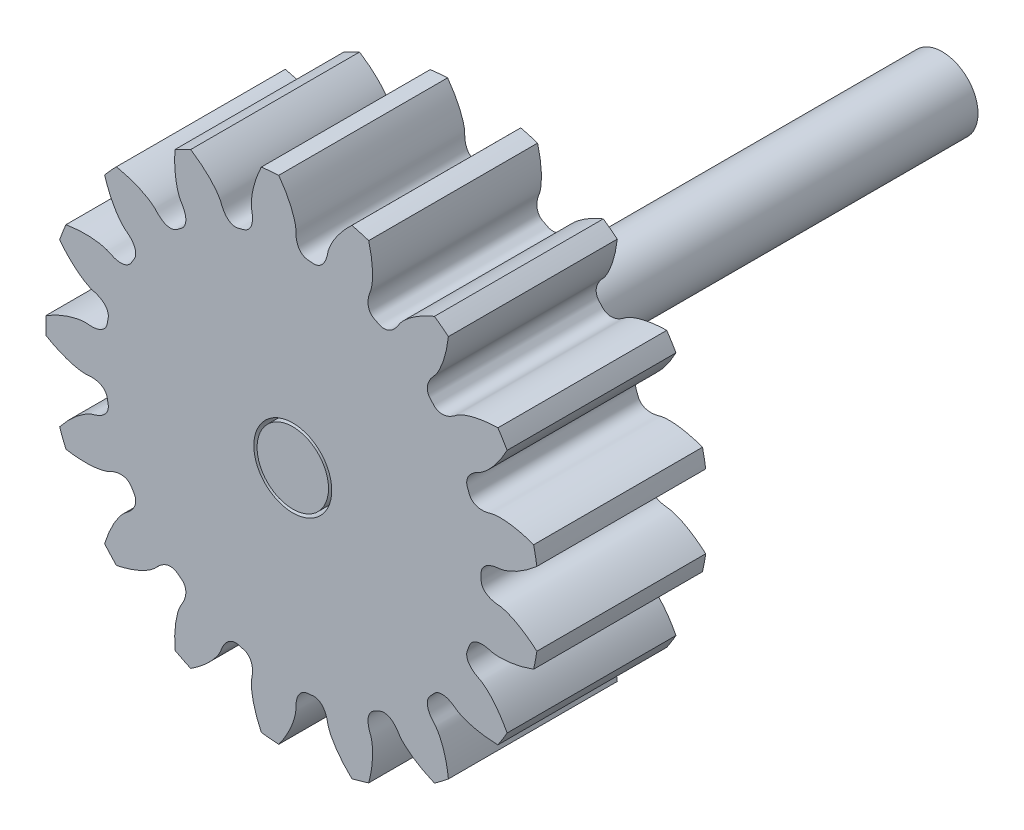
SolidWorks part; units mm, degrees
ref_plane "Front Plane" through (0, 0, 0) normal (0, 0, 1) x (1, 0, 0)
ref_plane "Top Plane" through (0, 0, 0) normal (0, 1, 0) x (1, 0, 0)
ref_plane "Right Plane" through (0, 0, 0) normal (1, 0, 0) x (0, 0, -1)
ref_axis "Axis1" through (0, 0, 55) along (0, 0, -1)
sketch "旋转草图大直齿轮" plane through (0, 0, 0) normal (1, 0, 0) x (0, 0, -1)
  line L0 (0, 0) -> (1, 0) construction
  line L1 (-10, 0) -> (-10, 19)
  line L2 (-10, 19) -> (3, 19)
  line L3 (3, 19) -> (3, 0)
  line L4 (3, 0) -> (-10, 0)
  dimension "Side1" = 10
  dimension "OutsideRadius" = 19
  dimension "Side2" = 3
revolve "大直齿轮" add sketch "旋转草图大直齿轮" angle 360 about L0
sketch "齿草图大直齿轮" plane through (0, 0, 0) normal (0, 0, 1) x (1, 0, 0)
  arc A0 (18.8777, 2.9059) -> (18.8777, -2.9059) centre (0, 0) cw
  spline S0 degree 3 poles (18.8777, -2.9059) (18.7162, -2.7605) (18.4737, -2.5555) (18.1462, -2.3058) (17.9156, -2.1416) (17.694, -1.9946) (17.4824, -1.8638) (17.2814, -1.7487) (17.092, -1.6481) (16.9148, -1.5614) (16.7504, -1.4876) (16.5997, -1.4257) (16.463, -1.3747) (16.3411, -1.3337) (16.2343, -1.3016) (16.143, -1.2774) (16.0678, -1.2601) (16.0089, -1.2485) (15.9082, -1.2318) (15.8073, -1.2291) (15.7037, -1.216) (15.6495, -1.2083) (15.5963, -1.1996) (15.544, -1.19) (15.4927, -1.1794) (15.4423, -1.1677) (15.3928, -1.1551) (15.3442, -1.1414) (15.2965, -1.1266) (15.2496, -1.1108) (15.2035, -1.0937) (15.1582, -1.0755) (15.1136, -1.056) (15.0698, -1.0351) (15.0267, -1.0127) (14.9843, -0.9888) (14.9426, -0.9632) (14.9016, -0.9357) (14.8613, -0.9062) (14.8218, -0.8744) (14.7832, -0.8402) (14.7455, -0.8034) (14.709, -0.7636) (14.674, -0.7206) (14.6407, -0.6743) (14.6095, -0.6245) (14.581, -0.5711) (14.5558, -0.5142) (14.5343, -0.4538) (14.5174, -0.3904) (14.5054, -0.3246) (14.4997, -0.2626) (14.4972, -0.1542) (14.5022, 0) (14.4972, 0.1542) (14.4997, 0.2626) (14.5054, 0.3246) (14.5174, 0.3904) (14.5343, 0.4538) (14.5558, 0.5142) (14.581, 0.5711) (14.6095, 0.6245) (14.6407, 0.6743) (14.674, 0.7206) (14.709, 0.7636) (14.7455, 0.8034) (14.7832, 0.8402) (14.8218, 0.8744) (14.8613, 0.9062) (14.9016, 0.9357) (14.9426, 0.9632) (14.9843, 0.9888) (15.0267, 1.0127) (15.0698, 1.0351) (15.1136, 1.056) (15.1582, 1.0755) (15.2035, 1.0937) (15.2496, 1.1108) (15.2965, 1.1266) (15.3442, 1.1414) (15.3928, 1.1551) (15.4423, 1.1677) (15.4927, 1.1794) (15.544, 1.19) (15.5963, 1.1996) (15.6495, 1.2083) (15.7037, 1.216) (15.8073, 1.2291) (15.9082, 1.2318) (16.0089, 1.2485) (16.0678, 1.2601) (16.143, 1.2774) (16.2343, 1.3016) (16.3411, 1.3337) (16.463, 1.3747) (16.5997, 1.4257) (16.7504, 1.4876) (16.9148, 1.5614) (17.092, 1.6481) (17.2814, 1.7487) (17.4824, 1.8638) (17.694, 1.9946) (17.9156, 2.1416) (18.1462, 2.3058) (18.4737, 2.5555) (18.7162, 2.7605) (18.8777, 2.9059) knots 0 0 0 0 0.058344 0.085213 0.110547 0.134345 0.156608 0.177336 0.196528 0.214185 0.230306 0.244893 0.257943 0.269459 0.279439 0.287883 0.294792 0.300166 0.304005 0.32219 0.327162 0.332059 0.336883 0.341638 0.346326 0.350953 0.355523 0.36004 0.36451 0.36894 0.373335 0.377703 0.382053 0.386393 0.390734 0.395086 0.399462 0.403875 0.408338 0.412867 0.417479 0.422188 0.427012 0.431965 0.437063 0.442315 0.447728 0.453304 0.459035 0.464908 0.470898 0.476975 0.481621 0.5 0.518379 0.523025 0.529102 0.535092 0.540965 0.546696 0.552272 0.557685 0.562937 0.568035 0.572988 0.577812 0.582521 0.587133 0.591662 0.596125 0.600538 0.604914 0.609266 0.613607 0.617947 0.622297 0.626665 0.63106 0.63549 0.63996 0.644477 0.649047 0.653674 0.658362 0.663117 0.667941 0.672838 0.67781 0.695995 0.699834 0.705208 0.712117 0.720561 0.730541 0.742057 0.755107 0.769694 0.785815 0.803472 0.822664 0.843392 0.865655 0.889453 0.914787 0.941656 1 1 1 1
extrude "齿拉伸切除大直齿轮" cut sketch "齿草图大直齿轮" against normal blind 10 and the other way blind 10
pattern_circular "齿形大直齿轮" count 17 every 21.176 about axis through (0, 0, 55) along (0, 0, -1) of "齿拉伸切除大直齿轮"
sketch "孔旋转草图" plane through (0, 0, 0) normal (1, 0, 0) x (0, 0, -1)
  line L0 (0, 0) -> (1, 0) construction
  line L1 (-10, 0) -> (10, 0)
  line L2 (10, 0) -> (10, 3)
  line L3 (10, 3) -> (-10, 3)
  line L4 (-10, 3) -> (-10, 0)
  dimension "BoreSide1" = 10
  dimension "BoreSide2" = 10
  dimension "D1" = 3
revolve "孔旋转切除" cut sketch "孔旋转草图" angle 360 about L0
sketch "辅助草图大直齿轮" plane through (0, 0, 0) normal (0, 0, 1) x (1, 0, 0)
  circle A0 centre (0, 0) radius 17 construction
  circle A1 centre (0, 0) radius 15.9748 construction
  circle A2 centre (0, 0) radius 15.9784 construction
  circle A3 centre (0, 0) radius 19 construction
  circle A4 centre (0, 0) radius 14.5 construction
  dimension "PitchDiameter" = 34
  dimension "BaseDiameter" = 31.9495
  dimension "FormDiameter" = 31.9568
  dimension "MajorDiameter" = 38
  dimension "MinorDiameter" = 29
sketch "Sketch1" plane through (0, 0, 10) normal (0, 0, 1) x (1, 0, 0)
  circle A0 centre (0, 0) radius 2.75
  dimension "D1" = 5.5
extrude "Extrude1" add sketch "Sketch1" against normal blind 50 separate body
